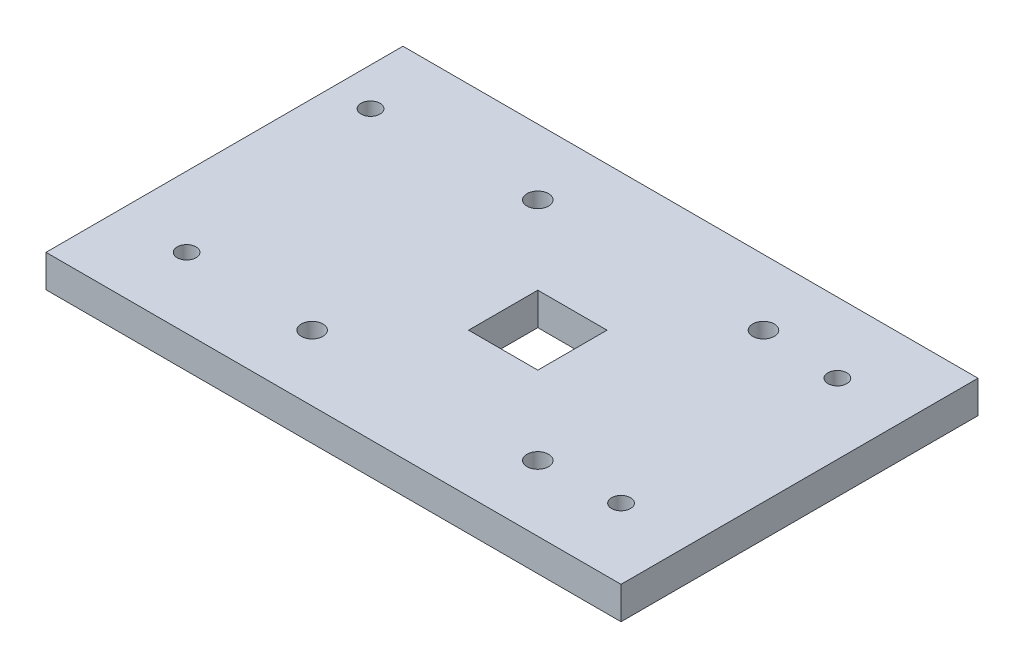
SolidWorks part; units mm, degrees
ref_plane "Front Plane" through (0, 0, 0) normal (0, 0, 1) x (1, 0, 0)
ref_plane "Top Plane" through (0, 0, 0) normal (0, 1, 0) x (1, 0, 0)
ref_plane "Right Plane" through (0, 0, 0) normal (1, 0, 0) x (0, 0, -1)
sketch "Sketch1" plane through (0, 0, 0) normal (0, 1, 0) x (1, 0, 0)
  line L0 (-57.93, -33) -> (48.39, -33)
  line L1 (-57.93, -33) -> (-57.93, 33)
  line L2 (48.39, -33) -> (48.39, 33)
  line L3 (-57.93, 33) -> (48.39, 33)
  line L6 (-6.4, 6.4) -> (6.4, 6.4)
  line L7 (-6.4, 6.4) -> (-6.4, -6.4)
  line L8 (6.4, 6.4) -> (6.4, -6.4)
  line L9 (-6.4, -6.4) -> (6.4, -6.4)
  circle A4 centre (20.8625, -20.8625) radius 2
  circle A5 centre (20.8625, 20.8625) radius 2
  circle A6 centre (-20.8625, -20.8625) radius 2
  circle A7 centre (-20.8625, 20.8625) radius 2
  point P1 (0, 0)
  dimension "D12" = 20.8625
  dimension "D16" = 20.8625
  dimension "D1" = 66
  dimension "D2" = 106.32
  dimension "D3" = 12.8
  dimension "D4" = 6.4
  dimension "D5" = 48.39
  dimension "D6" = 33
  dimension "D7" = 6.4
  dimension "D8" = 12.8
  dimension "D9" = 20.8625
  dimension "D10" = 20.8625
  dimension "D11" = 20.8625
  dimension "D13" = 20.8625
  dimension "D14" = 20.8625
  dimension "D15" = 20.8625
extrude "Boss-Extrude1" add sketch "Sketch1" along normal blind 6
sketch "Sketch4" plane through (0, 6, 0) normal (0, 1, 0) x (1, 0, 0)
  line L0 (48.39, 33) -> (-57.93, 33) construction
  line L1 (-57.93, 33) -> (-57.93, -33) construction
  line L2 (-57.93, -33) -> (48.39, -33) construction
  line L3 (48.39, -33) -> (48.39, 33) construction
  circle A0 centre (-50.93, 20) radius 1.75
  circle A1 centre (-44.93, -20) radius 1.75
  circle A2 centre (35.39, -20) radius 1.75
  circle A3 centre (35.39, 20) radius 1.75
  dimension "D1" = 13
  dimension "D2" = 7
  dimension "D3" = 3.5
  dimension "D4" = 3.5
  dimension "D7" = 3.5
  dimension "D8" = 13
  dimension "D9" = 13
  dimension "D10" = 3.5
  dimension "D11" = 13
  dimension "D12" = 13
  dimension "D5" = 13
  dimension "D6" = 13
extrude "Cut-Extrude1" cut sketch "Sketch4" against normal through all
